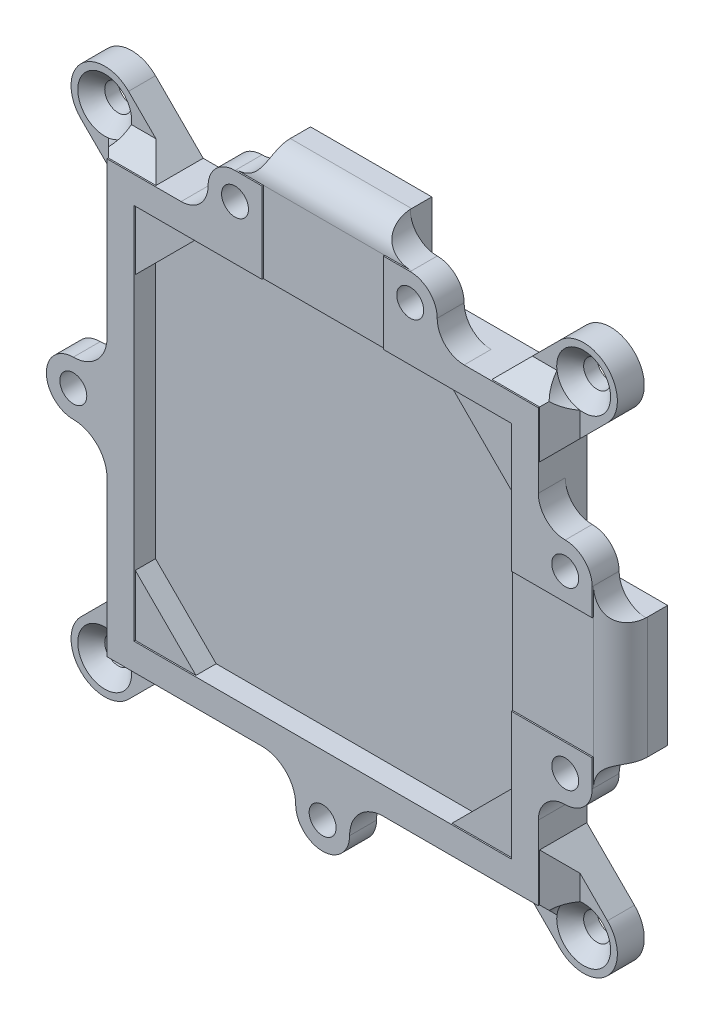
SolidWorks part; units mm, degrees
ref_plane "Top Plane" through (0, 0, 0) normal (0, 0, 1) x (1, 0, 0)
ref_plane "Right Plane" through (0, 0, 0) normal (0, 1, 0) x (1, 0, 0)
ref_plane "Front Plane" through (0, 0, 0) normal (1, 0, 0) x (0, 0, -1)
sketch "Sketch1" plane through (0, 0, 0) normal (0, 0, 1) x (1, 0, 0)
  line L0 (-32, -32) -> (-32, 32)
  line L1 (-28, -28) -> (28, -28) construction
  line L2 (-28, -28) -> (-28, 28) construction
  line L3 (-28, 28) -> (28, 28) construction
  line L4 (28, -28) -> (28, 28) construction
  line L5 (-28, -28) -> (28, 28) construction
  line L6 (-28, 28) -> (28, -28) construction
  line L7 (-32, 32) -> (32, 32)
  line L8 (32, -32) -> (32, 32)
  line L9 (-32, -32) -> (32, -32)
  point P0 (0, 0)
  dimension "D1" = 56
  dimension "D2" = 4
extrude "Boss-Extrude1" add sketch "Sketch1" along normal blind 4
sketch "Sketch2" plane through (0, 0, 4) normal (0, 0, 1) x (1, 0, 0)
  line L0 (-28, -28) -> (28, -28) construction
  line L1 (28, -28) -> (28, 28) construction
  line L2 (-28, 28) -> (28, 28) construction
  line L3 (-28, -28) -> (-28, 28) construction
  line L4 (-28, -28) -> (28, -28)
  line L5 (28, -28) -> (28, 28)
  line L6 (-28, 28) -> (28, 28)
  line L7 (-28, -28) -> (-28, 28)
  line L12 (-32, -32) -> (32, -32)
  line L13 (32, -32) -> (32, 32)
  line L14 (32, 32) -> (-32, 32)
  line L15 (-32, 32) -> (-32, -32)
  line L16 (-32, -32) -> (32, -32)
  line L17 (32, -32) -> (32, 32)
  line L18 (32, 32) -> (-32, 32)
  line L19 (-32, 32) -> (-32, -32)
  dimension "D1" = 0
extrude "Boss-Extrude2" add sketch "Sketch2" along normal blind 3
chamfer "Chamfer4" distance 9 angle 45 4 edges at (-28, 28, 5.5) (28, 28, 5.5) (28, -28, 5.5) (-28, -28, 5.5)
sketch "Sketch3" plane through (0, 0, 7) normal (0, 0, 1) x (1, 0, 0)
  line L0 (-9, 32) -> (-9, 28)
  line L1 (19, 28) -> (-19, 28) construction
  line L4 (-32, 32) -> (-32, -32)
  line L5 (-32, -32) -> (32, -32)
  line L6 (32, -32) -> (32, 32)
  line L7 (32, 32) -> (-32, 32)
  line L8 (-32, 32) -> (-32, -32)
  line L9 (-32, -32) -> (32, -32)
  line L10 (32, -32) -> (32, -9)
  line L11 (32, 32) -> (9, 32)
  line L12 (9, 28) -> (9, 32)
  line L13 (28, -19) -> (28, 19) construction
  line L15 (28, 9) -> (32, 9)
  line L16 (19, 28) -> (-19, 28) construction
  line L18 (32, -9) -> (28, -9)
  line L21 (9, 28) -> (-9, 28) construction
  line L22 (-9, 32) -> (-32, 32)
  line L23 (9, 32) -> (-9, 32) construction
  line L24 (32, 9) -> (32, 32)
  line L25 (32, -9) -> (32, 9) construction
  line L27 (28, -9) -> (28, 9) construction
  line L28 (28, 9) -> (28, 28)
  line L29 (28, 28) -> (9, 28)
  line L30 (-9, 28) -> (-28, 28)
  line L31 (-28, 28) -> (-28, -28)
  line L32 (-28, -28) -> (28, -28)
  line L33 (28, -28) -> (28, -9)
  line L34 (-19, -28) -> (19, -28) construction
  line L35 (-28, 19) -> (-28, -19) construction
  dimension "D2" = 18
  dimension "D1" = 0
extrude "Boss-Extrude3" add sketch "Sketch3" along normal blind 10
sketch "Sketch4" plane through (0, 0, 0) normal (0, 0, -1) x (-1, 0, 0)
  line L0 (-32, -32) -> (-32, 32) construction
  line L1 (-32, -9) -> (-49, -9)
  line L2 (-32, -9) -> (-32, 9)
  line L3 (-32, 9) -> (-49, 9)
  line L5 (-62, 9) -> (-62, 22) construction
  line L6 (-62, -22) -> (-85, -22)
  line L7 (-62, -22) -> (-62, -9) construction
  line L8 (-62, 22) -> (-85, 22)
  line L9 (-85, -22) -> (-85, 22)
  line L10 (-62, -9) -> (-62, 9) construction
  line L11 (-62, 22) -> (-49, 9)
  line L12 (-49, 9) -> (-62, 9) construction
  line L13 (-49, -9) -> (-62, -22)
  line L14 (-49, -9) -> (-62, -9) construction
  point P12 (-32, 0)
  dimension "D1" = 44
  dimension "D2" = 23
  dimension "D3" = 53
extrude "Boss-Extrude4" add sketch "Sketch4" against normal up to surface (7 mm away) up to face at (30, 0, 7)
ref_axis "Axis1" through (0, 0, 12.6) along (0, 0, -1)
pattern_circular "CirPattern1" count 2 every 90 about axis through (0, 0, 12.6) along (0, 0, -1) of "Boss-Extrude4" reverse direction yes
fillet "Fillet1" radius 3 4 edges at (-9, 32, 3.5) (9, 32, 3.5) (32, 9, 3.5) (32, -9, 3.5)
sketch "Sketch5" plane through (0, 0, 0) normal (0, 0, -1) x (-1, 0, 0)
  line L0 (24.9289, -32) -> (32, -39.0711)
  line L1 (32, -32) -> (-32, -32) construction
  line L2 (39.0711, -32) -> (32, -24.9289)
  line L3 (32, 32) -> (32, -32) construction
  line L4 (32, -24.9289) -> (32, -32)
  line L5 (32, -32) -> (24.9289, -32)
  line L6 (35.5355, -35.5355) -> (32, -32) construction
  line L7 (24.9289, -32) -> (32, -24.9289) construction
  circle A0 centre (35.5355, -35.5355) radius 2
  arc A1 (32, -39.0711) -> (39.0711, -32) centre (35.5355, -35.5355) ccw
  point P15 (24.9289, -32)
  dimension "D1" = 10
  dimension "D2" = 4
  dimension "D3" = 5
extrude "Boss-Extrude5" add sketch "Sketch5" against normal blind 4
pattern_circular "CirPattern3" count 4 every 90 about axis through (0, 0, 12.6) along (0, 0, -1) of "Boss-Extrude5"
chamfer "Chamfer2" distance 3 angle 45 8 edges at (-28.4645, -32, 4) (-32, -28.4645, 4) (28.4645, -32, 4) (32, -28.4645, 4) (32, 28.4645, 4) (28.4645, 32, 4) (-32, 28.4645, 4) (-28.4645, 32, 4)
ref_plane "Plane1" through (0, 0, 0) normal (0.7071, -0.7071, 0) x (-0.7071, -0.7071, 0)
sketch "Sketch6" plane through (0, 0, 0) normal (0.7071, -0.7071, 0) x (-0.7071, -0.7071, 0)
  line L0 (50.2548, -10) -> (50.2548, 0)
  line L1 (50.2548, 0) -> (48.2548, 0)
  line L2 (48.2548, 0) -> (48.2548, -2)
  line L4 (46.2548, -4) -> (46.2548, -10)
  line L5 (46.2548, -10) -> (50.2548, -10)
  line L11 (48.2548, -4) -> (52.2548, -4) construction
  line L14 (46.2548, -4) -> (48.2548, -2)
  line L15 (48.2548, -4) -> (46.2548, -4) construction
  line L17 (48.2548, -2) -> (48.2548, -4) construction
  point P2 (50.2548, -4)
  point P12 (52.2548, -4)
  dimension "D1" = 2
  dimension "D2" = 10
revolve "Cut-Revolve1" cut sketch "Sketch6" angle 360 about L0
pattern_circular "CirPattern4" count 4 every 90 about axis through (0, 0, 12.6) along (0, 0, -1) of "Cut-Revolve1"
sketch "Sketch7" plane through (0, 0, 17) normal (0, 0, 1) x (1, 0, 0)
  line L1 (32, 32) -> (-32, 32)
  line L2 (32, 32) -> (32, -32)
  line L3 (32, -32) -> (-32, -32)
  line L4 (-32, 32) -> (-32, -32)
extrude "Cut-Extrude1" cut sketch "Sketch7" against normal offset from surface (9.8 mm away) 0.2 up to face at (25, 25, 7)
sketch "Sketch8" plane through (0, 0, 7.2) normal (0, 0, 1) x (1, 0, 0)
  line L0 (-37, 0) -> (0, 0) construction
  line L1 (-32, -32) -> (-32, 32) construction
  line L2 (-37, 9) -> (-37, -9) construction
  line L3 (-21, 32) -> (-21, 28)
  line L4 (-9, 35) -> (-9, 49) construction
  line L5 (-9, 36) -> (-9, 32)
  line L6 (-9, 32) -> (-9, 28)
  line L7 (-9, 28) -> (-28, 28) construction
  line L8 (-9, 28) -> (-9, 32) construction
  line L9 (-9, 28) -> (-21, 28)
  line L11 (0, -3.96) -> (0, 3.96) construction
  line L12 (9, 44) -> (9, 36)
  line L17 (-32, 9) -> (-32, -9)
  line L19 (-9, 44) -> (-9, 36)
  line L20 (-13, 36) -> (-13, 40) construction
  line L21 (9, 36) -> (9, 32)
  line L27 (-13, 36) -> (-9, 32) construction
  line L28 (-32, 32) -> (-9, 32) construction
  line L29 (-21, 36) -> (-13, 36) construction
  line L30 (9, 32) -> (9, 28)
  line L31 (9, 28) -> (21, 28)
  line L32 (21, 32) -> (21, 28)
  circle A1 centre (-13, 36) radius 2
  circle A2 centre (-37, 0) radius 2
  circle A3 centre (13, 36) radius 2
  arc A4 (17, 36) -> (21, 32) centre (21, 36) ccw
  arc A5 (-37, 4) -> (-37, -4) centre (-37, 0) ccw
  arc A6 (-32, 9) -> (-37, 4) centre (-37, 9) cw
  arc A7 (-37, -4) -> (-32, -9) centre (-37, -9) cw
  arc A8 (-13, 40) -> (-17, 36) centre (-13, 36) ccw
  arc A11 (-13, 40) -> (-9, 44) centre (-13, 44) ccw
  arc A15 (-17, 36) -> (-21, 32) centre (-21, 36) cw
  arc A16 (13, 40) -> (17, 36) centre (13, 36) cw
  arc A17 (13, 40) -> (9, 44) centre (13, 44) cw
  point P10 (-13, 36)
  dimension "D1" = 4
  dimension "D2" = 5
  dimension "D3" = 2
  dimension "D4" = 45
  dimension "D5" = 2
extrude "Boss-Extrude6" add sketch "Sketch8" against normal blind 4
sketch "Sketch9" plane through (0, 0, 0) normal (-1, 0, 0) x (0, 0, 1)
  line L0 (7, 44) -> (7, 49) construction
  line L2 (3, 44) -> (0, 44)
  line L3 (12, 85) -> (0, 85)
  line L4 (12, 85) -> (12, 40)
  line L5 (12, 40) -> (7, 40)
  line L7 (0, 44) -> (0, 85)
  line L8 (7, 85) -> (0, 85) construction
  line L9 (7, 62) -> (7, 85) construction
  line L10 (7.2, 28) -> (7, 28) construction
  line L11 (7, 40) -> (7, 44) construction
  line L12 (7, 44) -> (3, 44) construction
  line L13 (0, 62) -> (0, 85) construction
  arc A0 (7, 40) -> (3, 44) centre (3, 40) ccw
  point P20 (7, 40)
  dimension "D1" = 5
  dimension "D2" = 4
  dimension "D3" = 12
extrude "Cut-Extrude2" cut sketch "Sketch9" against normal through all both and the other way through all
mirror "Mirror2" about plane through (0, 0, 0) normal (0.7071, -0.7071, 0) of "Cut-Extrude2", "Boss-Extrude6"
chamfer "Chamfer5" distance 2 angle 45 2 edges at (-32, 0, 3.2) (0, -32, 3.2)
sketch "Sketch12" plane through (0, 0, 0) normal (0, 0, -1) x (-1, 0, 0)
  line L0 (35.5355, 35.5355) -> (-35.5355, -35.5355) construction
  text T0 "<b>HRG</b>\r\n" font "Century Gothic" height 10
extrude "Cut-Extrude3" cut sketch "Sketch12" against normal blind 0.6
